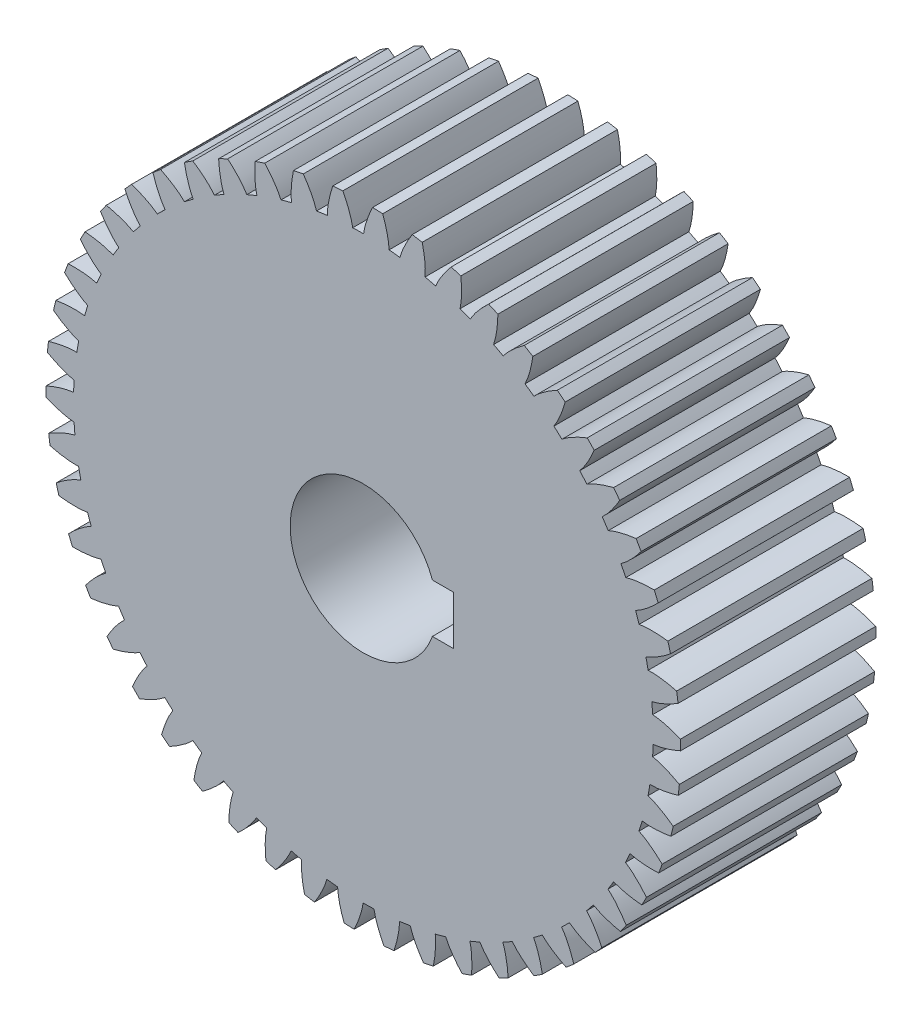
SolidWorks part; units mm, degrees
ref_plane "Front Plane" through (0, 0, 0) normal (0, 0, 1) x (1, 0, 0)
ref_plane "Top Plane" through (0, 0, 0) normal (0, 1, 0) x (1, 0, 0)
ref_plane "Right Plane" through (0, 0, 0) normal (1, 0, 0) x (0, 0, -1)
sketch "Involute Geometry" plane through (0, 0, 0) normal (0, 0, 1) x (1, 0, 0)
  line L0 (0, 23.4923) -> (0, 0) construction
  line L1 (0, 0) -> (1.1665, 25.9738) construction
  line L2 (2.1059, 23.3977) -> (0, 0) construction
  line L3 (0.3366, 24.9977) -> (0, 0) construction
  line L4 (0, 0) -> (1.9056, 24.9273) construction
  circle A1 centre (0, 0) radius 23.4923 construction
  circle A2 centre (0, 0) radius 25 construction
  circle A3 centre (0, 0) radius 26 construction
  circle A4 centre (0, 0) radius 23.75 construction
  arc A5 (0.7536, 25.9891) -> (1.5791, 25.952) centre (0, 0) cw
  arc A6 (0.3366, 24.9977) -> (1.9056, 24.9273) centre (0, 0) cw construction
  spline S0 degree 4 poles (0, 23.4923) (0, 23.5114) (0.0013, 23.5648) (0.0089, 23.6656) (0.0287, 23.8296) (0.081, 24.1325) (0.1926, 24.5862) (0.3554, 25.0766) (0.5626, 25.5852) (0.7677, 26.0245) (0.9438, 26.37) (1.171, 26.7822) (1.4642, 27.2682) (1.8332, 27.8211) (2.2875, 28.4323) (2.7797, 29.0321) (3.2982, 29.6089) (3.8411, 30.1634) (4.4053, 30.6951) (4.9175, 31.1416) (5.3665, 31.5096) (5.7503, 31.8087) (6.0572, 32.04) (6.3766, 32.2711) (6.6846, 32.4876) (7.0225, 32.7147) (7.3185, 32.909) (7.7622, 33.1868) (8.0307, 33.348) (8.4647, 33.6019) (8.6612, 33.7084) (8.8384, 33.8077) (8.891, 33.8352) (8.9294, 33.8561) (8.9501, 33.8675) knots 0 0 0 0 0 0.005377 0.015084 0.028532 0.04661 0.092111 0.146842 0.174209 0.201575 0.228941 0.256307 0.307035 0.361767 0.4165 0.471232 0.525964 0.580697 0.635429 0.690161 0.717528 0.744894 0.77226 0.799626 0.826992 0.854358 0.881725 0.909091 0.954545 0.977273 0.988636 0.994318 1 1 1 1 1 construction
  spline S1 degree 4 poles (0, 23.4923) (0, 23.5114) (0.0013, 23.5648) (0.0089, 23.6656) (0.0287, 23.8296) (0.081, 24.1325) (0.1926, 24.5862) (0.3554, 25.0766) (0.5626, 25.5852) (0.7677, 26.0245) (0.9438, 26.37) (1.171, 26.7822) (1.4642, 27.2682) (1.8332, 27.8211) (2.2875, 28.4323) (2.7797, 29.0321) (3.2982, 29.6089) (3.8411, 30.1634) (4.4053, 30.6951) (4.9175, 31.1416) (5.3665, 31.5096) (5.7503, 31.8087) (6.0572, 32.04) (6.3766, 32.2711) (6.6846, 32.4876) (7.0225, 32.7147) (7.3185, 32.909) (7.6041, 33.0878) (7.7558, 33.1811) (7.8311, 33.2268) knots 0 0 0 0 0 0.005377 0.015084 0.028532 0.04661 0.092111 0.146842 0.174209 0.201575 0.228941 0.256307 0.307035 0.361767 0.4165 0.471232 0.525964 0.580697 0.635429 0.690161 0.717528 0.744894 0.77226 0.799626 0.826992 0.854358 0.881725 0.909091 0.909091 0.909091 0.909091 0.909091
  spline S3 degree 4 poles (2.1059, 23.3977) (2.1076, 23.4167) (2.1111, 23.47) (2.1125, 23.5712) (2.1075, 23.7362) (2.0826, 24.0426) (2.0121, 24.5045) (1.8939, 25.0075) (1.7332, 25.5326) (1.5683, 25.9886) (1.4238, 26.3485) (1.2345, 26.7793) (0.9861, 27.2897) (0.6681, 27.8734) (0.2705, 28.5229) (-0.166, 29.1644) (-0.6307, 29.7854) (-1.1217, 30.3863) (-1.636, 30.9664) (-2.1061, 31.457) (-2.5203, 31.8638) (-2.8757, 32.1961) (-3.1606, 32.454) (-3.4581, 32.7128) (-3.7454, 32.9561) (-4.0616, 33.2125) (-4.339, 33.4325) (-4.756, 33.749) (-5.009, 33.9336) (-5.4185, 34.2255) (-5.6047, 34.3491) (-5.7723, 34.4639) (-5.8222, 34.4959) (-5.8585, 34.5202) (-5.8781, 34.5334) knots 0 0 0 0 0 0.005377 0.015084 0.028532 0.04661 0.092111 0.146842 0.174209 0.201575 0.228941 0.256307 0.307035 0.361767 0.4165 0.471232 0.525964 0.580697 0.635429 0.690161 0.717528 0.744894 0.77226 0.799626 0.826992 0.854358 0.881725 0.909091 0.954545 0.977273 0.988636 0.994318 1 1 1 1 1 construction
  spline S4 degree 4 poles (2.1059, 23.3977) (2.1076, 23.4167) (2.1111, 23.47) (2.1125, 23.5712) (2.1075, 23.7362) (2.0826, 24.0426) (2.0121, 24.5045) (1.8939, 25.0075) (1.7332, 25.5326) (1.5683, 25.9886) (1.4238, 26.3485) (1.2345, 26.7793) (0.9861, 27.2897) (0.6681, 27.8734) (0.2705, 28.5229) (-0.166, 29.1644) (-0.6307, 29.7854) (-1.1217, 30.3863) (-1.636, 30.9664) (-2.1061, 31.457) (-2.5203, 31.8638) (-2.8757, 32.1961) (-3.1606, 32.454) (-3.4581, 32.7128) (-3.7454, 32.9561) (-4.0616, 33.2125) (-4.339, 33.4325) (-4.6074, 33.6362) (-4.7502, 33.7427) (-4.8211, 33.795) knots 0 0 0 0 0 0.005377 0.015084 0.028532 0.04661 0.092111 0.146842 0.174209 0.201575 0.228941 0.256307 0.307035 0.361767 0.4165 0.471232 0.525964 0.580697 0.635429 0.690161 0.717528 0.744894 0.77226 0.799626 0.826992 0.854358 0.881725 0.909091 0.909091 0.909091 0.909091 0.909091
  dimension "D5" = 3.6
sketch "Sketch2" plane through (0, 0, 0) normal (0, 0, 1) x (1, 0, 0)
  circle A0 centre (0, 0) radius 23.75 construction
  circle A1 centre (0, 0) radius 23.75
extrude "Boss-Extrude1" add sketch "Sketch2" along normal mid plane 16
sketch "Sketch3" plane through (0, 0, 0) normal (0, 0, 1) x (1, 0, 0)
  arc A3 (0.0199, 23.75) -> (2.1092, 23.6562) centre (0, 0) cw
  arc A4 (1.5791, 25.952) -> (0.7536, 25.9891) centre (0, 0) ccw construction
  arc A5 (1.5791, 25.952) -> (0.7536, 25.9891) centre (0, 0) ccw
  circle A7 centre (0, 0) radius 23.75 construction
  spline S0 degree 4 poles (999.8204, 40.2462) (20.7121, 20.125) (0.4503, 21.1025) (-0.1347, 22.474) (0.0287, 23.8296) (0.081, 24.1325) (0.1926, 24.5862) (0.3554, 25.0766) (0.5626, 25.5852) (0.7677, 26.0245) (0.9438, 26.37) (1.171, 26.7822) (1.4642, 27.2682) (1.8332, 27.8211) (2.2875, 28.4323) (2.7797, 29.0321) (3.2982, 29.6089) (3.8411, 30.1634) (4.4053, 30.6951) (4.9175, 31.1416) (5.3665, 31.5096) (5.7503, 31.8087) (6.0572, 32.04) (6.3766, 32.2711) (6.6846, 32.4876) (7.0225, 32.7147) (8.3806, 33.6059) (11.7895, 35.5553) (-19.6779, 16.1915) (862.8738, 551.731) knots -0.338747 -0.338747 -0.338747 -0.338747 -0.338747 0.005377 0.015084 0.028532 0.04661 0.092111 0.146842 0.174209 0.201575 0.228941 0.256307 0.307035 0.361767 0.4165 0.471232 0.525964 0.580697 0.635429 0.690161 0.717528 0.744894 0.77226 0.799626 0.826992 0.854358 0.881725 1.301773 1.301773 1.301773 1.301773 1.301773 only from (0, 23.4923) to (7.5082, 22.3415) construction
  spline S1 degree 4 poles (0.0199, 23.75) (0.0244, 23.7861) (0.0384, 23.8856) (0.0837, 24.1434) (0.1926, 24.5862) (0.3677, 25.1136) (0.5556, 25.5675) (0.6944, 25.8667) (0.7536, 25.9891) knots 0.018251 0.018251 0.018251 0.018251 0.018251 0.028532 0.04661 0.092111 0.146842 0.185208 0.185208 0.185208 0.185208 0.185208
  spline S3 degree 4 poles (-992.1874, 129.7099) (-18.8247, 21.9006) (1.4432, 21.0579) (2.1488, 22.3715) (2.1075, 23.7362) (2.0826, 24.0426) (2.0121, 24.5045) (1.8939, 25.0075) (1.7332, 25.5326) (1.5683, 25.9886) (1.4238, 26.3485) (1.2345, 26.7793) (0.9861, 27.2897) (0.6681, 27.8734) (0.2705, 28.5229) (-0.166, 29.1644) (-0.6307, 29.7854) (-1.1217, 30.3863) (-1.636, 30.9664) (-2.1061, 31.457) (-2.5203, 31.8638) (-2.8757, 32.1961) (-3.1606, 32.454) (-3.4581, 32.7128) (-3.7454, 32.9561) (-4.0616, 33.2125) (-5.3344, 34.2219) (-8.5548, 36.469) (21.0501, 14.3623) (-809.9417, 626.8594) knots -0.338747 -0.338747 -0.338747 -0.338747 -0.338747 0.005377 0.015084 0.028532 0.04661 0.092111 0.146842 0.174209 0.201575 0.228941 0.256307 0.307035 0.361767 0.4165 0.471232 0.525964 0.580697 0.635429 0.690161 0.717528 0.744894 0.77226 0.799626 0.826992 0.854358 0.881725 1.301773 1.301773 1.301773 1.301773 1.301773 only from (2.1059, 23.3977) to (-4.8211, 33.795) construction
  spline S4 degree 4 poles (2.1092, 23.6562) (2.1079, 23.6925) (2.1029, 23.7929) (2.0809, 24.0537) (2.0121, 24.5045) (1.885, 25.0455) (1.7385, 25.5144) (1.6271, 25.8248) (1.5791, 25.952) knots 0.018251 0.018251 0.018251 0.018251 0.018251 0.028532 0.04661 0.092111 0.146842 0.185208 0.185208 0.185208 0.185208 0.185208
extrude "Boss-Extrude2" add sketch "Sketch3" along normal through all and the other way through all
fillet "Fillet2" [suppressed] radius 0.381
pattern_circular "CirPattern1" count 50 over 360 about axis through (0, 0, 8) along (0, 0, -1) of "Boss-Extrude2", "Fillet2"
ref_axis "Axis1" through (0, 0, 8) along (0, 0, -1)
sketch "Sketch4" plane through (0, 0, -8) normal (0, 0, -1) x (-1, 0, 0)
  circle A1 centre (0, 0) radius 6
  dimension "D1" = 12
extrude "Cut-Extrude1" cut sketch "Sketch4" against normal through all
sketch "Sketch5" plane through (0, 0, -8) normal (0, 0, -1) x (-1, 0, 0)
  line L7 (-7.4, -2) -> (-3.4, -2)
  line L8 (-7.4, -2) -> (-7.4, 2)
  line L9 (-7.4, 2) -> (-3.4, 2)
  line L10 (-3.4, -2) -> (-3.4, 2)
  line L11 (-7.4, -2) -> (-3.4, 2) construction
  line L12 (-7.4, 2) -> (-3.4, -2) construction
  circle A3 centre (0, 0) radius 6 construction
  point P0 (-5.065, 0)
  point P7 (-5.4, 0)
  point P13 (-4.0571, -2.0688)
  point P14 (0, 0)
  dimension "D1" = 2.6
  dimension "D3" = 4
extrude "Cut-Extrude2" cut sketch "Sketch5" against normal through all
equation "\"N\"= 50'Number of Teeth"
equation "\"m\"= 1mm'Diametral Pitch"
equation "\"phi\"= 20deg'Pressure Angle"
equation "\"a\"= \"m\"'Addendum"
equation "\"b\"= 1.25 * \"m\"'Dedendum"
equation "\"Dp\"= \"N\" * \"m\"'Pitch diameter"
equation "\"Db\"= \"Dp\" * cos ( \"phi\" )'Base diameter"
equation "\"D1@Involute Geometry\" = \"Db\""
equation "\"D2@Involute Geometry\" = \"Dp\""
equation "\"D3@Involute Geometry\" = \"Dp\" + 2 * \"a\""
equation "\"D4@Involute Geometry\" = \"Dp\" - 2 * \"b\""
equation "\"D1@CirPattern1\"=\"N\""
equation "\"D5@Involute Geometry\"=180/\"N\""
equation "\"D1@Boss-Extrude1\"=16*\"m\""
equation "\"alpha\"= sqr ( \"Dp\" ^ 2 - \"Db\" ^ 2 ) / \"Db\" * 180 / pi - \"phi\""
equation "\"beta\"= ( ( 360deg / \"N\" ) / 4 - \"alpha\" )"
